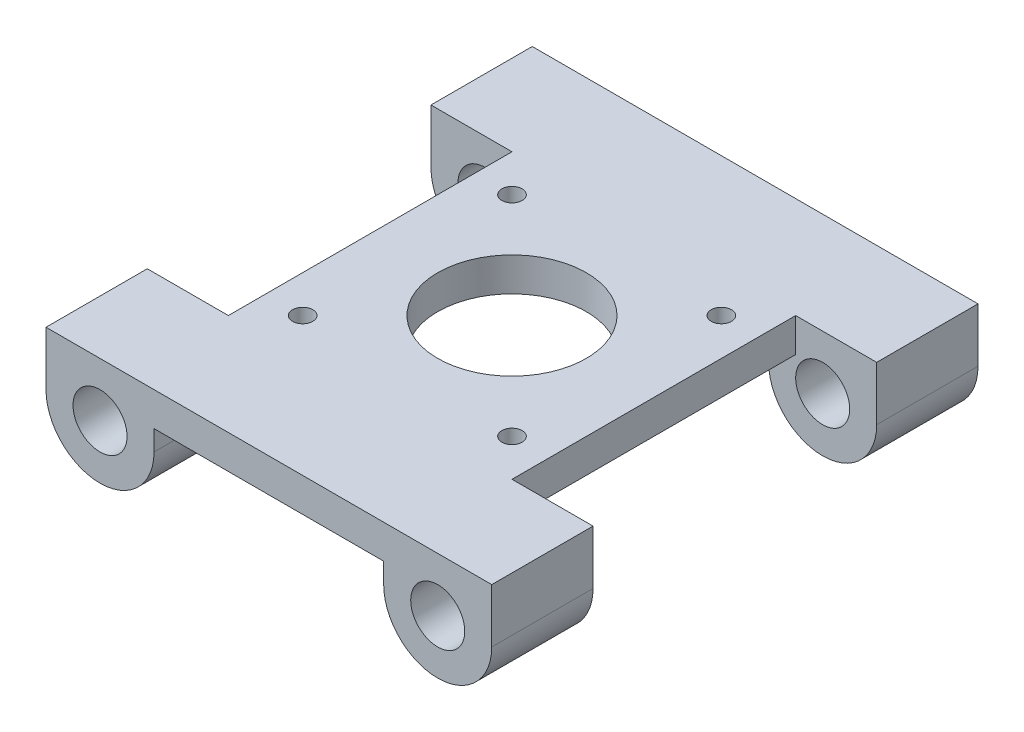
SolidWorks part; units mm, degrees
material "ABS"
ref_plane "Front Plane" through (0, 0, 0) normal (0, 0, 1) x (1, 0, 0)
ref_plane "Top Plane" through (0, 0, 0) normal (0, 1, 0) x (1, 0, 0)
ref_plane "Right Plane" through (0, 0, 0) normal (1, 0, 0) x (0, 0, -1)
sketch "Sketch1" plane through (0, 0, 0) normal (0, 0, 1) x (1, 0, 0)
  line L0 (0, 74.8863) -> (0, -94.3789) construction
  line L1 (33, 0) -> (-33, 0)
  line L2 (-33, 0) -> (-33, -8)
  line L3 (17, -5) -> (-17, -5)
  line L4 (-17, -5) -> (-17, -8)
  line L5 (17, -5) -> (17, -8)
  line L6 (33, 0) -> (33, -8)
  circle A0 centre (-25, -8) radius 4
  arc A1 (-33, -8) -> (-17, -8) centre (-25, -8) ccw
  arc A2 (33, -8) -> (17, -8) centre (25, -8) cw
  circle A3 centre (25, -8) radius 4
  point P16 (0, -5)
  point P17 (0, 0)
  dimension "D1" = 8
  dimension "D5" = 8
  dimension "D2" = 25
  dimension "D3" = 8
  dimension "D4" = 5
extrude "Boss-Extrude1" add sketch "Sketch1" against normal blind 15
sketch "Sketch2" plane through (0, 0, -15) normal (0, 0, -1) x (-1, 0, 0)
  line L0 (21, 0) -> (-21, 0)
  line L1 (-33, 0) -> (33, 0) construction
  line L2 (-21, 0) -> (-21, -5)
  line L3 (-21, -5) -> (21, -5)
  line L4 (17, -5) -> (-17, -5) construction
  line L5 (0, 7.9638) -> (0, -15.9981) construction
  line L6 (21, 0) -> (21, -5)
  point P12 (0, -5)
  point P13 (0, 0)
  dimension "D1" = 21
extrude "Boss-Extrude2" add sketch "Sketch2" along normal blind 42
extrude "Boss-Extrude3" add sketch "Sketch1<2>" against normal blind 15 from vertex starting at point (-21, 0, -57)
sketch "Sketch1<2>" plane through (0, 0, 0) normal (0, 0, 1) x (1, 0, 0) same geometry as "Sketch1"
sketch "Sketch3" plane through (0, 0, 0) normal (0, 1, 0) x (1, 0, 0)
  line L0 (0, -9.6218) -> (0, 80.5515) construction
  line L1 (-21, 36) -> (21, 36) construction
  line L2 (-21, 57) -> (-21, 15) construction
  line L3 (21, 57) -> (21, 15) construction
  circle A0 centre (-15.5, 51.5) radius 1.5
  circle A1 centre (0, 36) radius 11
  circle A2 centre (15.5, 51.5) radius 1.5
  circle A3 centre (15.5, 20.5) radius 1.5
  circle A4 centre (-15.5, 20.5) radius 1.5
  dimension "D1" = 3
  dimension "D4" = 22
  dimension "D2" = 15.5
  dimension "D3" = 15.5
  dimension "D5" = 2
  dimension "D6" = 2
extrude "Cut-Extrude1" cut sketch "Sketch3" against normal through all
equation "\"rod_diameter\"= 8"
equation "\"rod_hole_thickness\"= 4"
equation "\"rod_radius\"= \"rod_diameter\" / 2"
equation "\"platter_diameter\"= 320"
equation "\"platter_radius\"= \"platter_diameter\" / 2"
equation "\"extruder_mount_hole_spacing\"= 50"
equation "\"arm_rod_spacing\"= 40"
equation "\"top_frame_rod_spacing\"= \"arm_rod_spacing\" + 40"
equation "\"motor_level_rod_spacing\"= 15"
equation "\"linear_bearing_diameter\"= 15"
equation "\"z_rod_spacing\"= 75"
equation "\"platter_rod_spacing\"= 50"
equation "\"rod_nut_thickness\"= 6.5"
equation "\"rod_nut_inscribed_diameter\"= 13"
equation "\"z_height\"= 350"
equation "\"D1@Sketch1\"=\"rod_diameter\""
equation "\"D2@Sketch1\"=\"platter_rod_spacing\"/2"
equation "\"D3@Sketch1\"=\"rod_radius\"+\"rod_hole_thickness\""
equation "\"D5@Sketch1\"=\"rod_radius\"+\"rod_hole_thickness\""
equation "\"D2@Sketch3\"=31/2"
